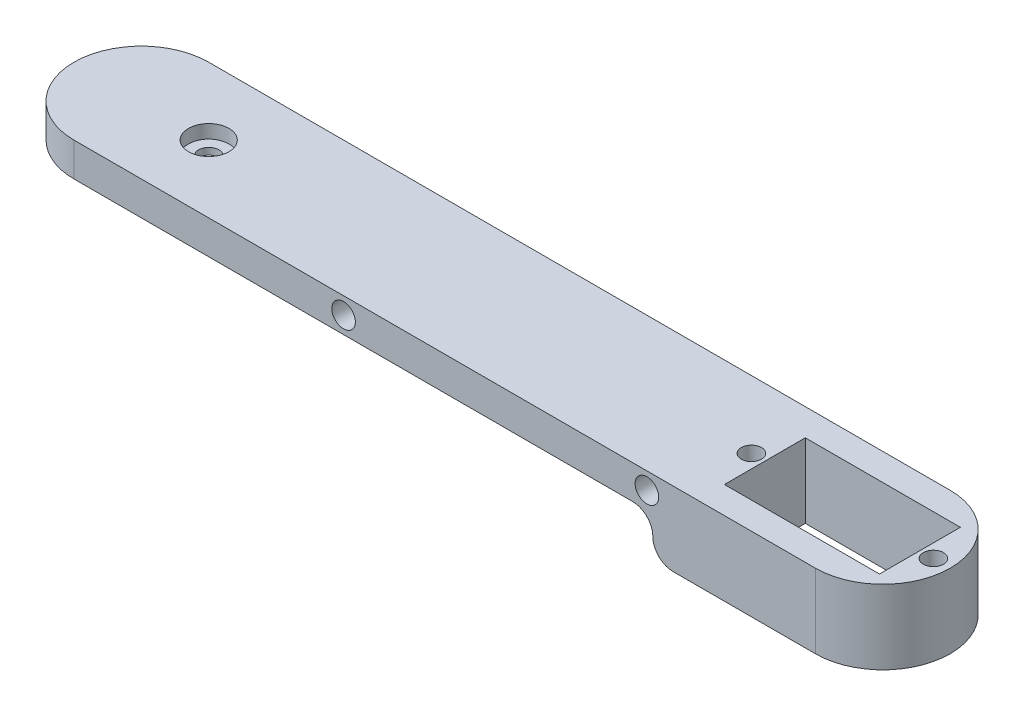
SolidWorks part; units mm, degrees
ref_plane "Front Plane" through (0, 0, 0) normal (0, 0, 1) x (1, 0, 0)
ref_plane "Top Plane" through (0, 0, 0) normal (0, 1, 0) x (1, 0, 0)
ref_plane "Right Plane" through (0, 0, 0) normal (1, 0, 0) x (0, 0, -1)
sketch "Sketch1" plane through (0, 0, 0) normal (0, 1, 0) x (1, 0, 0)
  line L1 (-40, 10) -> (40, 10)
  line L3 (-40, -10) -> (40, -10)
  line L6 (-40, 10) -> (-70, 10)
  line L8 (-40, -10) -> (-70, -10)
  arc A0 (40, -10) -> (40, 10) centre (40, 0) ccw
  arc A3 (-70, 10) -> (-70, -10) centre (-70, 0) ccw
  point P0 (0, 0)
  point P10 (-70, 10)
  dimension "D1" = 80
  dimension "D2" = 20
extrude "Boss-Extrude1" add sketch "Sketch1" along normal blind 5
sketch "Sketch5" plane through (0, 5, 0) normal (0, 1, 0) x (1, 0, 0)
  circle A0 centre (-70, 0) radius 3
  point P0 (-70, 0)
  dimension "D1" = 6
extrude "Cut-Extrude2" cut sketch "Sketch5" against normal blind 2
sketch "Sketch6" plane through (0, 0, 0) normal (0, -1, 0) x (1, 0, 0)
  line L0 (-70, 10) -> (-70, -10)
  line L2 (-50, 3) -> (-70, 6.6047)
  line L3 (-90, 3) -> (-70, 6.6047)
  line L4 (-90, -3) -> (-70, -6.5)
  line L5 (-70, -6.5) -> (-50, -3)
  circle A0 centre (-70, 0) radius 6.5
  circle A1 centre (-50, 0) radius 3
  circle A2 centre (-90, 0) radius 3
  point P7 (-90, 0)
  point P8 (-50, 0)
  arc M11 (-70, 10) -> (-70, -10) centre (-70, 0) ccw
  dimension "D1" = 13
  dimension "D4" = 6
  dimension "D5" = 6
  dimension "D2" = 20
  dimension "D3" = 20
extrude "Cut-Extrude3" cut sketch "Sketch6" against normal blind 2 contours A1 L2 A0 L5 | L5 A0 L0 | L0 A0 L4 | A2 L4 L3 M11 | A0 L3 L4 M11 | A1 | A2 region at (-83.4607, 0, 0.0216) region at (-77.3293, 0, 0.0691) region at (-67.2377, 0, 0.0139) region at (-72.7623, 0, 0.0139) region at (-58.9202, 0, 0.0401) region at (-90, 0, 0) region at (-50, 0, 0)
sketch "Sketch8" plane through (0, 3, 0) normal (0, 1, 0) x (1, 0, 0)
  circle A0 centre (-70, 0) radius 1.5
  dimension "D1" = 3
extrude "Cut-Extrude4" cut sketch "Sketch8" against normal through all
sketch "Sketch10" plane through (0, 0, 0) normal (0, -1, 0) x (1, 0, 0)
  line L0 (30, 10) -> (30, -10)
  line L1 (-70, 10) -> (40, 10) construction
  line L2 (40, -10) -> (-70, -10) construction
  line L3 (30, -10) -> (40, -10)
  line L5 (40, 10) -> (30, 10)
  arc A0 (40, -10) -> (40, 10) centre (40, 0) ccw
  point P0 (-70, 0)
  point P1 (30, 0)
  dimension "D1" = 100
extrude "Cut-Extrude5" cut sketch "Sketch10" against normal through all
sketch "Sketch11" plane through (0, 0, 0) normal (0, -1, 0) x (1, 0, 0)
  line L0 (30, 10) -> (30, -10) construction
  line L1 (30, 10) -> (30, -10)
  arc A0 (30, -10) -> (30, 10) centre (30, 0) ccw
extrude "Boss-Extrude2" add sketch "Sketch11" against normal through all
sketch "Sketch12" plane through (0, 0, 0) normal (0, -1, 0) x (1, 0, 0)
  line L2 (12.5, 6) -> (35.5, 6)
  line L3 (12.5, 6) -> (12.5, -6)
  line L4 (12.5, -6) -> (35.5, -6)
  line L5 (35.5, 6) -> (35.5, -6)
  circle A0 centre (37.5, 0) radius 1
  circle A1 centre (10.5, 0) radius 1
  point P4 (30, 0)
  point P5 (35.5, 0)
  point P6 (37.5, 0)
  point P9 (35.5, 6)
  point P10 (35.5, -6)
  point P11 (12.5, 6)
  point P16 (10.5, 0)
  dimension "D7" = 2
  dimension "D8" = 2
  dimension "D1" = 5.5
  dimension "D2" = 2
  dimension "D3" = 6
  dimension "D4" = 6
  dimension "D5" = 23
  dimension "D6" = 2
extrude "Cut-Extrude7" cut sketch "Sketch12" against normal through all
sketch "Sketch14" plane through (0, 0, 0) normal (0, -1, 0) x (1, 0, 0)
  line L1 (-70, -10) -> (-80, -10)
  line L3 (-80, 10) -> (-70, 10)
  arc A0 (-80, 10) -> (-80, -10) centre (-80, 0) ccw
  arc A1 (-70, 10) -> (-70, -10) centre (-70, 0) ccw
  dimension "D1" = 10
extrude "Boss-Extrude5" add sketch "Sketch14" against normal blind 5
sketch "Sketch15" plane through (0, 0, 0) normal (0, -1, 0) x (1, 0, 0)
  line L1 (-90, 3) -> (-78.6318, 5.049)
  line L2 (-78.6318, 5.049) -> (-78.6702, -4.9827)
  line L3 (-78.6702, -4.9827) -> (-90, -3)
  arc A1 (-90, 3) -> (-90, -3) centre (-90, 0) ccw
  arc A2 (-80, 10) -> (-80, -10) centre (-80, 0) ccw construction
  point P5 (-70, 0)
  point P6 (-50, 0)
  point P8 (-90, 0)
  dimension "D3" = 6
  dimension "D1" = 20
  dimension "D2" = 20
extrude "Cut-Extrude8" cut sketch "Sketch15" against normal blind 2
sketch "Sketch16" plane through (0, 0, 0) normal (0, -1, 0) x (1, 0, 0)
  line L0 (5.8794, 10) -> (5.8794, -10)
  line L1 (-80, 10) -> (30, 10) construction
  line L2 (30, -10) -> (-80, -10) construction
  line L3 (5.8794, -10) -> (30, -10)
  line L5 (30, 10) -> (5.8794, 10)
  line L7 (12.5, 6) -> (35.5, 6)
  line L8 (12.5, 6) -> (12.5, -6)
  line L9 (12.5, -6) -> (35.5, -6)
  line L10 (35.5, 6) -> (35.5, -6)
  arc A0 (30, -10) -> (30, 10) centre (30, 0) ccw
  circle A1 centre (10.5, 0) radius 1
  circle A2 centre (37.5, 0) radius 1
extrude "Boss-Extrude6" add sketch "Sketch16" along normal blind 6
fillet "Fillet1" radius 3 1 edges at (5.8794, -6, 0) type face fillet first side face at (10.5, -6, -1) second side face at (5.8794, -3, 0)
fillet "Fillet2" radius 3 1 edges at (5.8794, 0, 0) type face fillet first side face at (5.8794, -1.5, 0) second side face at (-57.8647, 0, 0.5817)
sketch "Sketch17" plane through (0, 5, 0) normal (0, 1, 0) x (1, 0, 0)
  circle A0 centre (10.5, 0) radius 1.5
  circle A1 centre (37.5, 0) radius 1.5
  dimension "D1" = 3
  dimension "D2" = 3
extrude "Cut-Extrude9" cut sketch "Sketch17" against normal blind 4
sketch "Sketch18" plane through (0, 0, 10) normal (0, 0, 1) x (1, 0, 0)
  line L0 (30, 5) -> (30, -6) construction
  line L1 (-80, 5) -> (30, 5) construction
  circle A0 centre (5, 2.5) radius 1.75
  circle A1 centre (-40, 2.5) radius 1.75
  point P0 (5, 2.5)
  point P6 (-40, 2.5)
  dimension "D4" = 3.5
  dimension "D5" = 3.5
  dimension "D1" = 25
  dimension "D2" = 2.5
  dimension "D3" = 70
extrude "Cut-Extrude10" cut sketch "Sketch18" against normal blind 8
